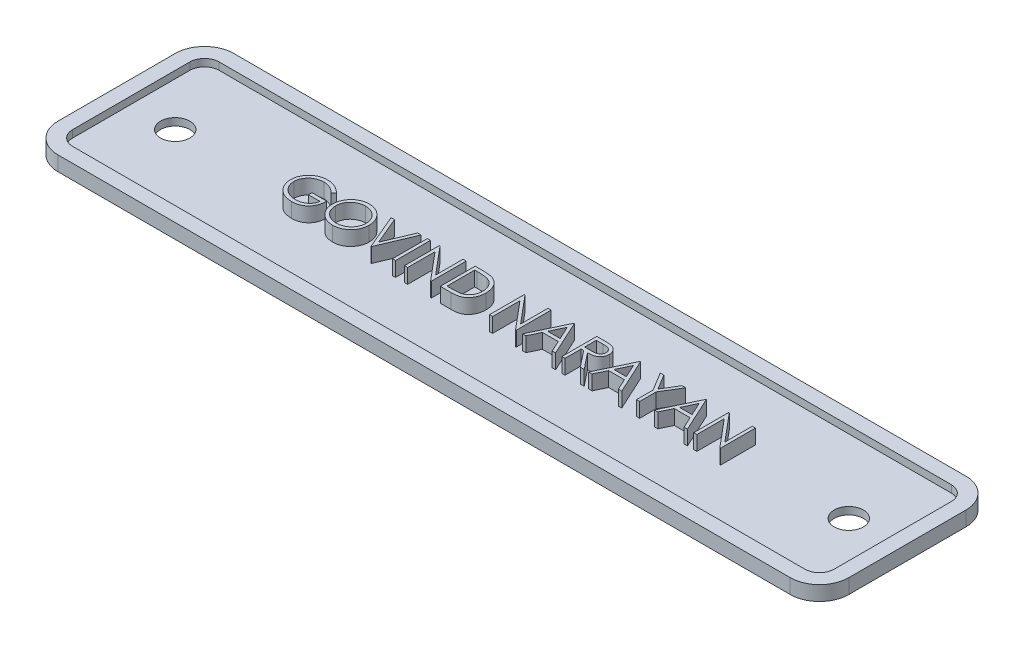
SolidWorks part; units mm, degrees
ref_plane "Front Plane" through (0, 0, 0) normal (0, 0, 1) x (1, 0, 0)
ref_plane "Top Plane" through (0, 0, 0) normal (0, 1, 0) x (1, 0, 0)
ref_plane "Right Plane" through (0, 0, 0) normal (1, 0, 0) x (0, 0, -1)
sketch "Sketch1" plane through (0, 0, 0) normal (0, 1, 0) x (1, 0, 0)
  line L0 (-25, 6) -> (25, 6)
  line L1 (-25, -5) -> (25, -5)
  line L2 (-26, -4) -> (-26, 4)
  line L3 (-25, 5) -> (25, 5)
  line L4 (26, -4) -> (26, 4)
  line L5 (27, -4) -> (27, 4)
  line L6 (-25, -6) -> (25, -6)
  line L7 (-27, -4) -> (-27, 4)
  line L12 (9.9022, 12.2527) -> (9.8154, 12.4822)
  arc A0 (25, 5) -> (26, 4) centre (25, 4) cw
  arc A1 (25, -5) -> (26, -4) centre (25, -4) ccw
  arc A2 (-25, -5) -> (-26, -4) centre (-25, -4) cw
  arc A3 (-26, 4) -> (-25, 5) centre (-25, 4) cw
  arc A4 (25, 6) -> (27, 4) centre (25, 4) cw
  arc A5 (25, -6) -> (27, -4) centre (25, -4) ccw
  arc A6 (-25, -6) -> (-27, -4) centre (-25, -4) cw
  arc A7 (-27, 4) -> (-25, 6) centre (-25, 4) cw
  circle A8 centre (-23, 0) radius 1
  circle A9 centre (23, 0) radius 1
  dimension "D1" = 1
  dimension "D3" = 5
  dimension "D4" = 5
  dimension "D5" = 2
  dimension "D6" = 2
  dimension "D2" = 1
  dimension "D7" = 12
extrude "Boss-Extrude1" add sketch "Sketch1" along normal blind 0.5 contours A3 L2 A2 L1 A1 L4 A0 L3 A8 A9 region at (0, 0, 0)
extrude "Boss-Extrude2" add sketch "Sketch1<3>" along normal blind 1 contours A7 L7 A6 L6 A5 L5 A4 L0 L2 A3 L3 A0 L4 A1 L1 A2 region at (0, 0, -5.4468)
sketch "Sketch1<3>" plane through (0, 0, 0) normal (0, 1, 0) x (1, 0, 0) same geometry as "Sketch1"
sketch "Sketch2" plane through (0, 0.5, 0) normal (0, 1, 0) x (1, 0, 0)
  text T0 "GOVIND NARAYAN" font "Century Gothic" height in points 9
extrude "Boss-Extrude3" add sketch "Sketch2" along normal blind 1
